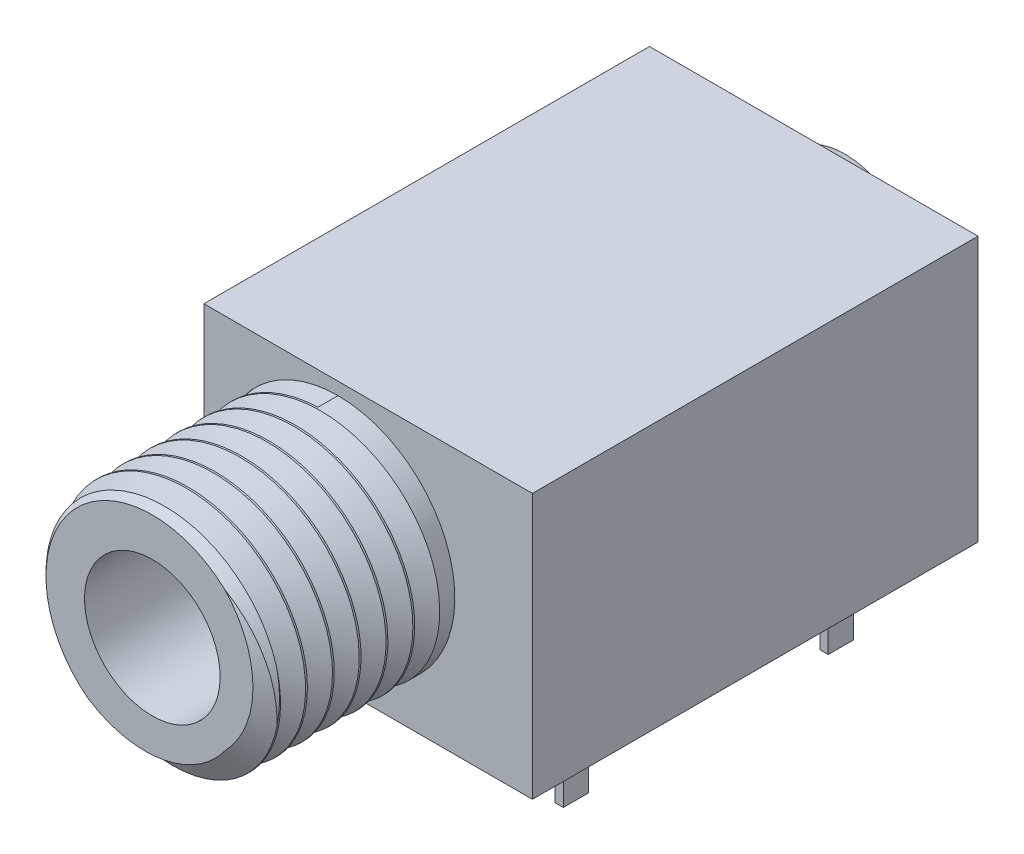
SolidWorks part; units mm, degrees
ref_plane "Front Plane" through (0, 0, 0) normal (0, 0, 1) x (1, 0, 0)
ref_plane "Top Plane" through (0, 0, 0) normal (0, 1, 0) x (1, 0, 0)
ref_plane "Right Plane" through (0, 0, 0) normal (1, 0, 0) x (0, 0, -1)
sketch "Sketch1" plane through (0, 0, 0) normal (0, 1, 0) x (1, 0, 0)
  line L1 (-14.6008, 12.6317) -> (1.1492, 12.6317)
  line L2 (-14.6008, 12.6317) -> (-14.6008, -8.7283)
  line L3 (-14.6008, -8.7283) -> (1.1492, -8.7283)
  line L4 (1.1492, 12.6317) -> (1.1492, -8.7283)
  dimension "D1" = 15.75
  dimension "D2" = 21.36
extrude "Boss-Extrude1" add sketch "Sketch1" along normal blind 12.7
sketch "Sketch3" plane through (0, 0, -12.6317) normal (0, 0, -1) x (-1, 0, 0)
  line L0 (-1.1492, 0) -> (14.6008, 0) construction
  line L1 (14.6008, 12.7) -> (14.6008, 0) construction
  circle A0 centre (8.1708, 6.5) radius 4
  dimension "D1" = 6.5
  dimension "D2" = 6.43
extrude "Boss-Extrude2" add sketch "Sketch3" along normal blind 2.94 draft 10
sketch "Sketch4" plane through (0, 0, 8.7283) normal (0, 0, 1) x (1, 0, 0)
  line L0 (-14.6008, 12.7) -> (-14.6008, 0) construction
  line L1 (-14.6008, 0) -> (1.1492, 0) construction
  circle A0 centre (-8.1708, 6.5) radius 5.6
  dimension "D1" = 6.43
  dimension "D2" = 6.5
extrude "Boss-Extrude3" add sketch "Sketch4" along normal blind 8.9
chamfer "Chamfer1" distance 0.5 angle 45 1 edges at (-2.5708, 6.5, 17.6283)
ref_plane "Plane1" through (0, 6.5, 0) normal (0, -1, 0) x (-1, 0, 0)
sketch "Sketch6" plane through (0, 6.5, 0) normal (0, -1, 0) x (-1, 0, 0)
  line L0 (13.7708, -16.5283) -> (13.7708, -17.7283)
  line L1 (13.7708, -17.1283) -> (13.7708, -8.7283) construction
  line L2 (2.5708, -17.1283) -> (13.7708, -17.1283) construction
  line L3 (13.7708, -17.7283) -> (12.7315, -17.1283)
  line L4 (12.7315, -17.1283) -> (13.7708, -16.5283)
  line L5 (8.1708, -18.6021) -> (8.1708, -10.6988) construction
  point P4 (13.7708, -17.1283)
  dimension "D1" = 5.6
  dimension "D3" = 1.2
sketch "Sketch9" plane through (0, 0, 17.6283) normal (0, 0, 1) x (1, 0, 0)
  circle A0 centre (-8.1708, 6.5) radius 5.6
curve "Helix/Spiral1" pitch 1.2857 height 9 radius 5.6 centre (-8.1708, 6.5, 17.6283) axis (0, 0, -1) start towards (0, 1, 0)
sweep "Cut-Sweep1" cut profiles "Sketch6" path "Helix/Spiral1"
sketch "Sketch13" plane through (0, 0, 17.6283) normal (0, 0, 1) x (1, 0, 0)
  circle A0 centre (-8.1708, 6.5) radius 3.25
  dimension "D1" = 6.5
extrude "Cut-Extrude1" cut sketch "Sketch13" against normal blind 29
sketch "Sketch14" plane through (0, 0, 0) normal (0, -1, 0) x (1, 0, 0)
  line L0 (-6.9358, -12.6317) -> (-6.9358, 8.7283) construction
  line L1 (-12.8508, 5.0783) -> (-12.4508, 5.0783)
  line L2 (-12.8508, 5.0783) -> (-12.8508, 3.8783)
  line L3 (-12.8508, 3.8783) -> (-12.4508, 3.8783)
  line L4 (-12.4508, 5.0783) -> (-12.4508, 3.8783)
  line L5 (-12.4508, -7.6217) -> (-12.4508, -8.8217)
  line L6 (-8.2508, -1.3881) -> (-8.2508, 3.8102) construction
  line L7 (-12.8508, -7.6217) -> (-12.8508, -8.8217)
  line L8 (-12.8508, -8.8217) -> (-12.4508, -8.8217)
  line L9 (-12.8508, -7.6217) -> (-12.4508, -7.6217)
  line L10 (-1.0208, -8.8217) -> (-1.4208, -8.8217)
  line L11 (-1.0208, 3.8783) -> (-1.4208, 3.8783)
  line L12 (-1.0208, 5.0783) -> (-1.0208, 3.8783)
  line L13 (-1.4208, 5.0783) -> (-1.4208, 3.8783)
  line L14 (-1.0208, 5.0783) -> (-1.4208, 5.0783)
  line L15 (-1.0208, -7.6217) -> (-1.0208, -8.8217)
  line L16 (-1.0208, -7.6217) -> (-1.4208, -7.6217)
  line L17 (-14.6008, -12.6317) -> (-14.6008, 8.7283) construction
  line L18 (-14.6008, 8.7283) -> (1.1492, 8.7283) construction
  line L19 (-1.4208, -7.6217) -> (-1.4208, -8.8217)
  dimension "D1" = 1.2
  dimension "D2" = 0.4
  dimension "D3" = 2
  dimension "D4" = 5.515
  dimension "D5" = 6.35
  dimension "D6" = 4.2
  dimension "D7" = 3.65
extrude "Boss-Extrude4" add sketch "Sketch14" along normal blind 3.25
